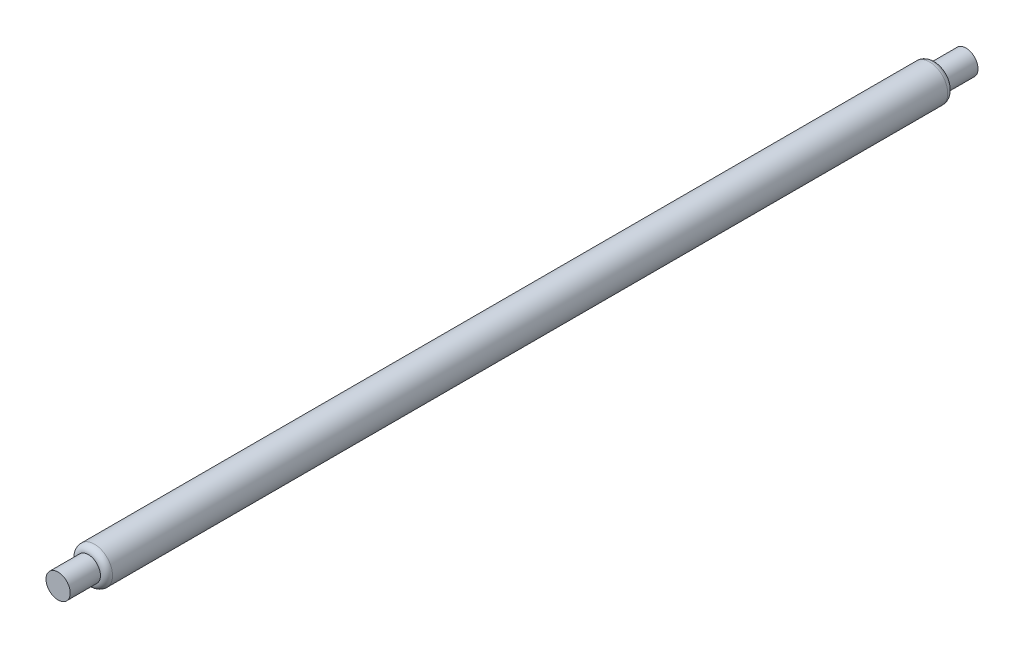
SolidWorks part; units mm, degrees
ref_plane "Front" through (0, 0, 0) normal (0, 0, 1) x (1, 0, 0)
ref_plane "Top" through (0, 0, 0) normal (0, 1, 0) x (1, 0, 0)
ref_plane "Right" through (0, 0, 0) normal (1, 0, 0) x (0, 0, -1)
sketch "Sketch1" plane through (0, 0, 0) normal (0, 0, 1) x (1, 0, 0)
  circle A0 centre (0, 0) radius 6
  dimension "D1" = 12
extrude "Boss-Extrude1" add sketch "Sketch1" along normal mid plane 300
sketch "Sketch2" plane through (0, 0, 150) normal (0, 0, 1) x (1, 0, 0)
  circle A0 centre (0, 0) radius 4
  circle A1 centre (0, 0) radius 6
  circle A2 centre (0, 0) radius 6 construction
  dimension "D1" = 8
extrude "Cut-Extrude1" cut sketch "Sketch2" against normal blind 10
fillet "Fillet1" radius 2 1 edges at (6, 0, 140)
mirror "Mirror1" about plane through (0, 0, 0) normal (0, 0, 1) of "Cut-Extrude1", "Fillet1"
equation "\"d\"= 12"
equation "\"l\"= 300"
equation "\"D1@Sketch1\"= \"d\""
equation "\"D1@Boss-Extrude1\"=\"l\""
equation "\"d_end\"= 8"
equation "\"D1@Sketch2\"=\"d_end\""
equation "\"l_end\"= 10"
equation "\"D1@Cut-Extrude1\"=\"l_end\""
equation "\"D1@Fillet1\"=(\"d\" - \"d_end\") / 2"
